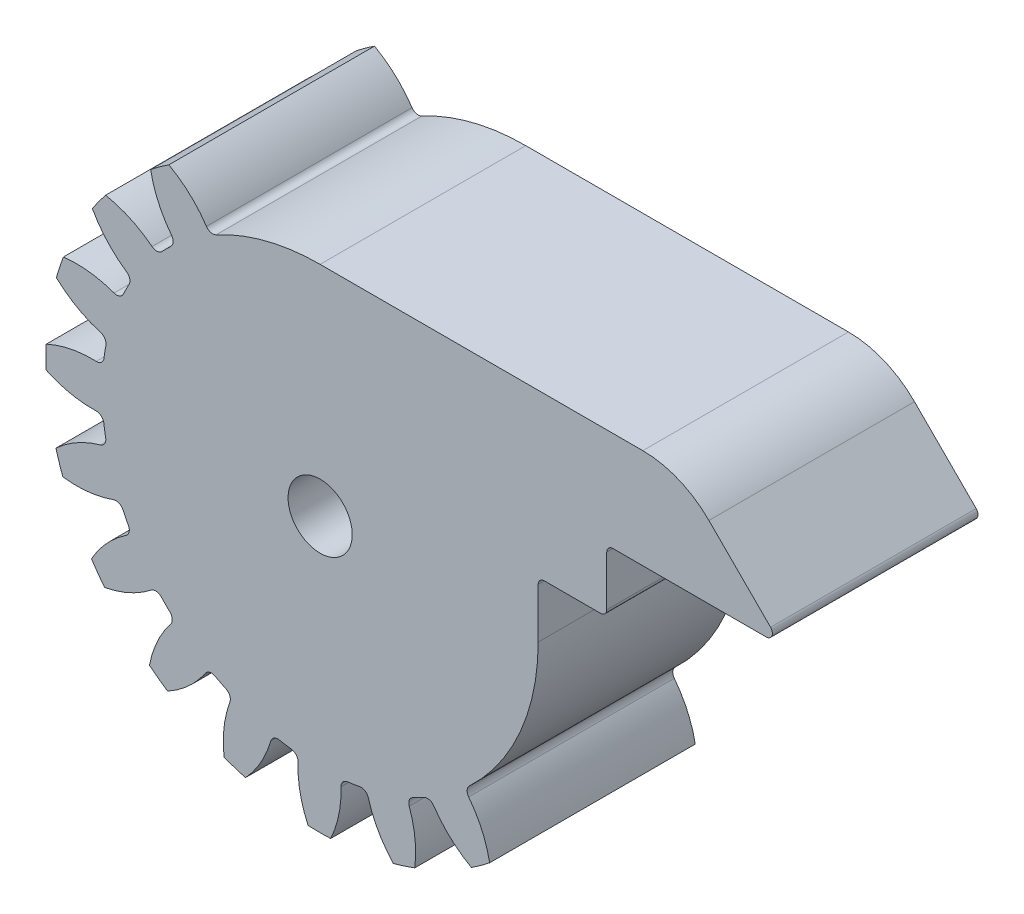
SolidWorks part; units mm, degrees
material "1023 Carbon Steel Sheet (SS)"
ref_plane "Front Plane" through (0, 0, 0) normal (0, 0, 1) x (1, 0, 0)
ref_plane "Top Plane" through (0, 0, 0) normal (0, 1, 0) x (1, 0, 0)
ref_plane "Right Plane" through (0, 0, 0) normal (1, 0, 0) x (0, 0, -1)
sketch "skBase" plane through (0, 0, 0) normal (0, 0, 1) x (1, 0, 0)
  circle A0 centre (0, 0) radius 20
  circle A1 centre (0, 0) radius 22
  circle A2 centre (0, 0) radius 17.5
  dimension "D1" = 40
  dimension "D3" = 4.5
extrude "Base" add sketch "skBase" along normal mid plane 16.5 contours A1
sketch "skToothProfile" plane through (0, 0, 0) normal (0, 0, 1) x (1, 0, 0)
  line L0 (0, 0) -> (0, 22) construction
  line L1 (-1.5692, 19.9383) -> (1.5692, 19.9383) construction
  line L2 (-1.0563, 17.4681) -> (0, 0) construction
  line L3 (0, 15.6271) -> (-2.6287, 22.8493) construction
  line L4 (0, 0) -> (3.4416, 21.7291) construction
  line L5 (1.5692, 19.9383) -> (4.6689, 19.4474) construction
  circle A0 centre (0, 0) radius 22 construction
  arc A1 (-1.0563, 17.4681) -> (-3.258, 22.7681) centre (-9.8105, 16.9387) ccw
  arc A2 (1.0563, 17.4681) -> (3.258, 22.7681) centre (9.8105, 16.9387) cw
  circle A3 centre (0, 0) radius 17.5 construction
  arc A4 (1.0563, 17.4681) -> (-1.0563, 17.4681) centre (0, 0) ccw
  circle A5 centre (0, 0) radius 20 construction
  circle A6 centre (0, 0) radius 22 construction
  circle A7 centre (0, 0) radius 23
  arc A8 (3.258, 22.7681) -> (-3.258, 22.7681) centre (0, 0) ccw
  dimension "D2" = 20
  dimension "D3" = 9
extrude "ToothProfile" cut sketch "skToothProfile" against normal through all and the other way through all
fillet "FilletToothProfile" radius 0.6 2 edges at (1.0563, 17.4681, 0) (-1.0563, 17.4681, 0)
pattern_circular "CirPatternTeeth" count 20 over 360 about axis through (0, 0, 8.25) along (0, 0, 1) of "ToothProfile", "FilletToothProfile"
sketch "skChaveta" plane through (0, 0, 8.25) normal (0, 0, 1) x (1, 0, 0)
  line L0 (0, 2.575) -> (0, 0) construction
  circle A0 centre (0, 0) radius 2.575
  dimension "D1" = 5.15
extrude "Chaveta" cut sketch "skChaveta" against normal through all contours A0
sketch "skRebaixo" plane through (0, 0, 8.25) normal (0, 0, 1) x (1, 0, 0)
  circle A0 centre (0, 0) radius 21.5
  circle A1 centre (0, 0) radius 7.5
  dimension "D1" = 43
  dimension "D2" = 15
sketch "Sketch4" plane through (0, 0, -8.25) normal (0, 0, -1) x (-1, 0, 0)
  circle A0 centre (0, 0) radius 17.5
  arc A5 (-2.5459, 21.8522) -> (-4.3314, 21.5694) centre (0, 0) ccw
  arc A6 (-2.5459, 21.8522) -> (-4.3314, 21.5694) centre (0, 0) ccw
  arc A7 (-18.0189, -1.107) -> (-21.8522, -2.5459) centre (-16.9387, -9.8105) ccw
  arc A8 (-18.0189, -1.107) -> (-21.8522, -2.5459) centre (-16.9387, -9.8105) ccw
  arc A9 (-21.5694, -4.3314) -> (-17.4791, -4.5153) centre (-19.1413, 4.096) ccw
  arc A10 (-21.5694, -4.3314) -> (-17.4791, -4.5153) centre (-19.1413, 4.096) ccw
  arc A127 (-19.996, -9.174) -> (-19.1752, -10.7848) centre (0, 0) ccw
  arc A128 (-19.996, -9.174) -> (-19.1752, -10.7848) centre (0, 0) ccw
  arc A129 (-16.1824, -14.904) -> (-14.904, -16.1824) centre (0, 0) ccw
  arc A130 (-16.1824, -14.904) -> (-14.904, -16.1824) centre (0, 0) ccw
  arc A131 (-10.7848, -19.1752) -> (-9.174, -19.996) centre (0, 0) ccw
  arc A132 (-10.7848, -19.1752) -> (-9.174, -19.996) centre (0, 0) ccw
  arc A133 (-4.3314, -21.5694) -> (-2.5459, -21.8522) centre (0, 0) ccw
  arc A134 (-4.3314, -21.5694) -> (-2.5459, -21.8522) centre (0, 0) ccw
  arc A135 (2.5459, -21.8522) -> (4.3314, -21.5694) centre (0, 0) ccw
  arc A136 (2.5459, -21.8522) -> (4.3314, -21.5694) centre (0, 0) ccw
  arc A137 (9.174, -19.996) -> (10.7848, -19.1752) centre (0, 0) ccw
  arc A138 (9.174, -19.996) -> (10.7848, -19.1752) centre (0, 0) ccw
  arc A139 (14.904, -16.1824) -> (16.1824, -14.904) centre (0, 0) ccw
  arc A140 (14.904, -16.1824) -> (16.1824, -14.904) centre (0, 0) ccw
  arc A141 (19.1752, -10.7848) -> (19.996, -9.174) centre (0, 0) ccw
  arc A142 (19.1752, -10.7848) -> (19.996, -9.174) centre (0, 0) ccw
  arc A143 (21.5694, -4.3314) -> (21.8522, -2.5459) centre (0, 0) ccw
  arc A144 (21.5694, -4.3314) -> (21.8522, -2.5459) centre (0, 0) ccw
  arc A145 (21.8522, 2.5459) -> (21.5694, 4.3314) centre (0, 0) ccw
  arc A146 (21.8522, 2.5459) -> (21.5694, 4.3314) centre (0, 0) ccw
  arc A147 (19.996, 9.174) -> (19.1752, 10.7848) centre (0, 0) ccw
  arc A148 (19.996, 9.174) -> (19.1752, 10.7848) centre (0, 0) ccw
  arc A149 (16.1824, 14.904) -> (14.904, 16.1824) centre (0, 0) ccw
  arc A150 (16.1824, 14.904) -> (14.904, 16.1824) centre (0, 0) ccw
  arc A151 (10.7848, 19.1752) -> (9.174, 19.996) centre (0, 0) ccw
  arc A152 (10.7848, 19.1752) -> (9.174, 19.996) centre (0, 0) ccw
  arc A153 (4.3314, 21.5694) -> (2.5459, 21.8522) centre (0, 0) ccw
  arc A154 (4.3314, 21.5694) -> (2.5459, 21.8522) centre (0, 0) ccw
  arc A155 (-9.174, 19.996) -> (-10.7848, 19.1752) centre (0, 0) ccw
  arc A156 (-9.174, 19.996) -> (-10.7848, 19.1752) centre (0, 0) ccw
  arc A157 (-14.904, 16.1824) -> (-16.1824, 14.904) centre (0, 0) ccw
  arc A158 (-14.904, 16.1824) -> (-16.1824, 14.904) centre (0, 0) ccw
  arc A159 (-19.1752, 10.7848) -> (-19.996, 9.174) centre (0, 0) ccw
  arc A160 (-19.1752, 10.7848) -> (-19.996, 9.174) centre (0, 0) ccw
  arc A161 (-21.5694, 4.3314) -> (-21.8522, 2.5459) centre (0, 0) ccw
  arc A162 (-21.5694, 4.3314) -> (-21.8522, 2.5459) centre (0, 0) ccw
  arc A163 (-4.3314, 21.5694) -> (-4.5153, 17.4791) centre (4.096, 19.1413) ccw
  arc A164 (-4.3314, 21.5694) -> (-4.5153, 17.4791) centre (4.096, 19.1413) ccw
  arc A165 (-4.9352, 16.7897) -> (-4.5153, 17.4791) centre (-5.1044, 17.3653) ccw
  arc A166 (-4.9352, 16.7897) -> (-4.5153, 17.4791) centre (-5.1044, 17.3653) ccw
  arc A167 (-4.9352, 16.7897) -> (-5.8761, 16.484) centre (0, 0) ccw
  arc A168 (-4.9352, 16.7897) -> (-5.8761, 16.484) centre (0, 0) ccw
  arc A169 (-6.621, 16.7949) -> (-5.8761, 16.484) centre (-6.0775, 17.0492) ccw
  arc A170 (-6.621, 16.7949) -> (-5.8761, 16.484) centre (-6.0775, 17.0492) ccw
  arc A171 (-6.621, 16.7949) -> (-9.174, 19.996) centre (-14.5647, 13.0781) ccw
  arc A172 (-6.621, 16.7949) -> (-9.174, 19.996) centre (-14.5647, 13.0781) ccw
  arc A173 (-10.7848, 19.1752) -> (-9.6956, 15.2283) centre (-2.0195, 19.4702) ccw
  arc A174 (-10.7848, 19.1752) -> (-9.6956, 15.2283) centre (-2.0195, 19.4702) ccw
  arc A175 (-9.882, 14.4429) -> (-9.6956, 15.2283) centre (-10.2208, 14.9381) ccw
  arc A176 (-9.882, 14.4429) -> (-9.6956, 15.2283) centre (-10.2208, 14.9381) ccw
  arc A177 (-9.882, 14.4429) -> (-10.6823, 13.8614) centre (0, 0) ccw
  arc A178 (-9.882, 14.4429) -> (-10.6823, 13.8614) centre (0, 0) ccw
  arc A179 (-11.4868, 13.9269) -> (-10.6823, 13.8614) centre (-11.0486, 14.3366) ccw
  arc A180 (-11.4868, 13.9269) -> (-10.6823, 13.8614) centre (-11.0486, 14.3366) ccw
  arc A181 (-11.4868, 13.9269) -> (-14.904, 16.1824) centre (-17.8932, 7.9372) ccw
  arc A182 (-11.4868, 13.9269) -> (-14.904, 16.1824) centre (-17.8932, 7.9372) ccw
  arc A183 (-16.1824, 14.904) -> (-13.9269, 11.4868) centre (-7.9372, 17.8932) ccw
  arc A184 (-16.1824, 14.904) -> (-13.9269, 11.4868) centre (-7.9372, 17.8932) ccw
  arc A185 (-13.8614, 10.6823) -> (-13.9269, 11.4868) centre (-14.3366, 11.0486) ccw
  arc A186 (-13.8614, 10.6823) -> (-13.9269, 11.4868) centre (-14.3366, 11.0486) ccw
  arc A187 (-13.8614, 10.6823) -> (-14.4429, 9.882) centre (0, 0) ccw
  arc A188 (-13.8614, 10.6823) -> (-14.4429, 9.882) centre (0, 0) ccw
  arc A189 (-15.2283, 9.6956) -> (-14.4429, 9.882) centre (-14.9381, 10.2208) ccw
  arc A190 (-15.2283, 9.6956) -> (-14.4429, 9.882) centre (-14.9381, 10.2208) ccw
  arc A191 (-15.2283, 9.6956) -> (-19.1752, 10.7848) centre (-19.4702, 2.0195) ccw
  arc A192 (-15.2283, 9.6956) -> (-19.1752, 10.7848) centre (-19.4702, 2.0195) ccw
  arc A193 (-19.996, 9.174) -> (-16.7949, 6.621) centre (-13.0781, 14.5647) ccw
  arc A194 (-19.996, 9.174) -> (-16.7949, 6.621) centre (-13.0781, 14.5647) ccw
  arc A195 (-16.484, 5.8761) -> (-16.7949, 6.621) centre (-17.0492, 6.0775) ccw
  arc A196 (-16.484, 5.8761) -> (-16.7949, 6.621) centre (-17.0492, 6.0775) ccw
  arc A197 (-16.484, 5.8761) -> (-16.7897, 4.9352) centre (0, 0) ccw
  arc A198 (-16.484, 5.8761) -> (-16.7897, 4.9352) centre (0, 0) ccw
  arc A199 (-17.4791, 4.5153) -> (-16.7897, 4.9352) centre (-17.3653, 5.1044) ccw
  arc A200 (-17.4791, 4.5153) -> (-16.7897, 4.9352) centre (-17.3653, 5.1044) ccw
  arc A201 (-17.4791, 4.5153) -> (-21.5694, 4.3314) centre (-19.1413, -4.096) ccw
  arc A202 (-17.4791, 4.5153) -> (-21.5694, 4.3314) centre (-19.1413, -4.096) ccw
  arc A203 (-21.8522, 2.5459) -> (-18.0189, 1.107) centre (-16.9387, 9.8105) ccw
  arc A204 (-21.8522, 2.5459) -> (-18.0189, 1.107) centre (-16.9387, 9.8105) ccw
  arc A205 (-17.493, 0.4946) -> (-18.0189, 1.107) centre (-18.0928, 0.5116) ccw
  arc A206 (-17.493, 0.4946) -> (-18.0189, 1.107) centre (-18.0928, 0.5116) ccw
  arc A207 (-17.493, 0.4946) -> (-17.493, -0.4946) centre (0, 0) ccw
  arc A208 (-17.493, 0.4946) -> (-17.493, -0.4946) centre (0, 0) ccw
  arc A209 (-18.0189, -1.107) -> (-17.493, -0.4946) centre (-18.0928, -0.5116) ccw
  arc A210 (-18.0189, -1.107) -> (-17.493, -0.4946) centre (-18.0928, -0.5116) ccw
  arc A211 (-16.7897, -4.9352) -> (-17.4791, -4.5153) centre (-17.3653, -5.1044) ccw
  arc A212 (-16.7897, -4.9352) -> (-17.4791, -4.5153) centre (-17.3653, -5.1044) ccw
  arc A213 (-16.7897, -4.9352) -> (-16.484, -5.8761) centre (0, 0) ccw
  arc A214 (-16.7897, -4.9352) -> (-16.484, -5.8761) centre (0, 0) ccw
  arc A215 (-16.7949, -6.621) -> (-16.484, -5.8761) centre (-17.0492, -6.0775) ccw
  arc A216 (-16.7949, -6.621) -> (-16.484, -5.8761) centre (-17.0492, -6.0775) ccw
  arc A217 (-16.7949, -6.621) -> (-19.996, -9.174) centre (-13.0781, -14.5647) ccw
  arc A218 (-16.7949, -6.621) -> (-19.996, -9.174) centre (-13.0781, -14.5647) ccw
  arc A219 (-19.1752, -10.7848) -> (-15.2283, -9.6956) centre (-19.4702, -2.0195) ccw
  arc A220 (-19.1752, -10.7848) -> (-15.2283, -9.6956) centre (-19.4702, -2.0195) ccw
  arc A221 (-14.4429, -9.882) -> (-15.2283, -9.6956) centre (-14.9381, -10.2208) ccw
  arc A222 (-14.4429, -9.882) -> (-15.2283, -9.6956) centre (-14.9381, -10.2208) ccw
  arc A223 (-14.4429, -9.882) -> (-13.8614, -10.6823) centre (0, 0) ccw
  arc A224 (-14.4429, -9.882) -> (-13.8614, -10.6823) centre (0, 0) ccw
  arc A225 (-13.9269, -11.4868) -> (-13.8614, -10.6823) centre (-14.3366, -11.0486) ccw
  arc A226 (-13.9269, -11.4868) -> (-13.8614, -10.6823) centre (-14.3366, -11.0486) ccw
  arc A227 (-13.9269, -11.4868) -> (-16.1824, -14.904) centre (-7.9372, -17.8932) ccw
  arc A228 (-13.9269, -11.4868) -> (-16.1824, -14.904) centre (-7.9372, -17.8932) ccw
  arc A229 (-14.904, -16.1824) -> (-11.4868, -13.9269) centre (-17.8932, -7.9372) ccw
  arc A230 (-14.904, -16.1824) -> (-11.4868, -13.9269) centre (-17.8932, -7.9372) ccw
  arc A231 (-10.6823, -13.8614) -> (-11.4868, -13.9269) centre (-11.0486, -14.3366) ccw
  arc A232 (-10.6823, -13.8614) -> (-11.4868, -13.9269) centre (-11.0486, -14.3366) ccw
  arc A233 (-10.6823, -13.8614) -> (-9.882, -14.4429) centre (0, 0) ccw
  arc A234 (-10.6823, -13.8614) -> (-9.882, -14.4429) centre (0, 0) ccw
  arc A235 (-9.6956, -15.2283) -> (-9.882, -14.4429) centre (-10.2208, -14.9381) ccw
  arc A236 (-9.6956, -15.2283) -> (-9.882, -14.4429) centre (-10.2208, -14.9381) ccw
  arc A237 (-9.6956, -15.2283) -> (-10.7848, -19.1752) centre (-2.0195, -19.4702) ccw
  arc A238 (-9.6956, -15.2283) -> (-10.7848, -19.1752) centre (-2.0195, -19.4702) ccw
  arc A239 (-9.174, -19.996) -> (-6.621, -16.7949) centre (-14.5647, -13.0781) ccw
  arc A240 (-9.174, -19.996) -> (-6.621, -16.7949) centre (-14.5647, -13.0781) ccw
  arc A241 (-5.8761, -16.484) -> (-6.621, -16.7949) centre (-6.0775, -17.0492) ccw
  arc A242 (-5.8761, -16.484) -> (-6.621, -16.7949) centre (-6.0775, -17.0492) ccw
  arc A243 (-5.8761, -16.484) -> (-4.9352, -16.7897) centre (0, 0) ccw
  arc A244 (-5.8761, -16.484) -> (-4.9352, -16.7897) centre (0, 0) ccw
  arc A245 (-4.5153, -17.4791) -> (-4.9352, -16.7897) centre (-5.1044, -17.3653) ccw
  arc A246 (-4.5153, -17.4791) -> (-4.9352, -16.7897) centre (-5.1044, -17.3653) ccw
  arc A247 (-4.5153, -17.4791) -> (-4.3314, -21.5694) centre (4.096, -19.1413) ccw
  arc A248 (-4.5153, -17.4791) -> (-4.3314, -21.5694) centre (4.096, -19.1413) ccw
  arc A249 (-2.5459, -21.8522) -> (-1.107, -18.0189) centre (-9.8105, -16.9387) ccw
  arc A250 (-2.5459, -21.8522) -> (-1.107, -18.0189) centre (-9.8105, -16.9387) ccw
  arc A251 (-0.4946, -17.493) -> (-1.107, -18.0189) centre (-0.5116, -18.0928) ccw
  arc A252 (-0.4946, -17.493) -> (-1.107, -18.0189) centre (-0.5116, -18.0928) ccw
  arc A253 (-0.4946, -17.493) -> (0.4946, -17.493) centre (0, 0) ccw
  arc A254 (-0.4946, -17.493) -> (0.4946, -17.493) centre (0, 0) ccw
  arc A255 (1.107, -18.0189) -> (0.4946, -17.493) centre (0.5116, -18.0928) ccw
  arc A256 (1.107, -18.0189) -> (0.4946, -17.493) centre (0.5116, -18.0928) ccw
  arc A257 (1.107, -18.0189) -> (2.5459, -21.8522) centre (9.8105, -16.9387) ccw
  arc A258 (1.107, -18.0189) -> (2.5459, -21.8522) centre (9.8105, -16.9387) ccw
  arc A259 (4.3314, -21.5694) -> (4.5153, -17.4791) centre (-4.096, -19.1413) ccw
  arc A260 (4.3314, -21.5694) -> (4.5153, -17.4791) centre (-4.096, -19.1413) ccw
  arc A261 (4.9352, -16.7897) -> (4.5153, -17.4791) centre (5.1044, -17.3653) ccw
  arc A262 (4.9352, -16.7897) -> (4.5153, -17.4791) centre (5.1044, -17.3653) ccw
  arc A263 (4.9352, -16.7897) -> (5.8761, -16.484) centre (0, 0) ccw
  arc A264 (4.9352, -16.7897) -> (5.8761, -16.484) centre (0, 0) ccw
  arc A265 (6.621, -16.7949) -> (5.8761, -16.484) centre (6.0775, -17.0492) ccw
  arc A266 (6.621, -16.7949) -> (5.8761, -16.484) centre (6.0775, -17.0492) ccw
  arc A267 (6.621, -16.7949) -> (9.174, -19.996) centre (14.5647, -13.0781) ccw
  arc A268 (6.621, -16.7949) -> (9.174, -19.996) centre (14.5647, -13.0781) ccw
  arc A269 (10.7848, -19.1752) -> (9.6956, -15.2283) centre (2.0195, -19.4702) ccw
  arc A270 (10.7848, -19.1752) -> (9.6956, -15.2283) centre (2.0195, -19.4702) ccw
  arc A271 (9.882, -14.4429) -> (9.6956, -15.2283) centre (10.2208, -14.9381) ccw
  arc A272 (9.882, -14.4429) -> (9.6956, -15.2283) centre (10.2208, -14.9381) ccw
  arc A273 (9.882, -14.4429) -> (10.6823, -13.8614) centre (0, 0) ccw
  arc A274 (9.882, -14.4429) -> (10.6823, -13.8614) centre (0, 0) ccw
  arc A275 (11.4868, -13.9269) -> (10.6823, -13.8614) centre (11.0486, -14.3366) ccw
  arc A276 (11.4868, -13.9269) -> (10.6823, -13.8614) centre (11.0486, -14.3366) ccw
  arc A277 (11.4868, -13.9269) -> (14.904, -16.1824) centre (17.8932, -7.9372) ccw
  arc A278 (11.4868, -13.9269) -> (14.904, -16.1824) centre (17.8932, -7.9372) ccw
  arc A279 (16.1824, -14.904) -> (13.9269, -11.4868) centre (7.9372, -17.8932) ccw
  arc A280 (16.1824, -14.904) -> (13.9269, -11.4868) centre (7.9372, -17.8932) ccw
  arc A281 (13.8614, -10.6823) -> (13.9269, -11.4868) centre (14.3366, -11.0486) ccw
  arc A282 (13.8614, -10.6823) -> (13.9269, -11.4868) centre (14.3366, -11.0486) ccw
  arc A283 (13.8614, -10.6823) -> (14.4429, -9.882) centre (0, 0) ccw
  arc A284 (13.8614, -10.6823) -> (14.4429, -9.882) centre (0, 0) ccw
  arc A285 (15.2283, -9.6956) -> (14.4429, -9.882) centre (14.9381, -10.2208) ccw
  arc A286 (15.2283, -9.6956) -> (14.4429, -9.882) centre (14.9381, -10.2208) ccw
  arc A287 (15.2283, -9.6956) -> (19.1752, -10.7848) centre (19.4702, -2.0195) ccw
  arc A288 (15.2283, -9.6956) -> (19.1752, -10.7848) centre (19.4702, -2.0195) ccw
  arc A289 (19.996, -9.174) -> (16.7949, -6.621) centre (13.0781, -14.5647) ccw
  arc A290 (19.996, -9.174) -> (16.7949, -6.621) centre (13.0781, -14.5647) ccw
  arc A291 (16.484, -5.8761) -> (16.7949, -6.621) centre (17.0492, -6.0775) ccw
  arc A292 (16.484, -5.8761) -> (16.7949, -6.621) centre (17.0492, -6.0775) ccw
  arc A293 (16.484, -5.8761) -> (16.7897, -4.9352) centre (0, 0) ccw
  arc A294 (16.484, -5.8761) -> (16.7897, -4.9352) centre (0, 0) ccw
  arc A295 (17.4791, -4.5153) -> (16.7897, -4.9352) centre (17.3653, -5.1044) ccw
  arc A296 (17.4791, -4.5153) -> (16.7897, -4.9352) centre (17.3653, -5.1044) ccw
  arc A297 (17.4791, -4.5153) -> (21.5694, -4.3314) centre (19.1413, 4.096) ccw
  arc A298 (17.4791, -4.5153) -> (21.5694, -4.3314) centre (19.1413, 4.096) ccw
  arc A299 (21.8522, -2.5459) -> (18.0189, -1.107) centre (16.9387, -9.8105) ccw
  arc A300 (21.8522, -2.5459) -> (18.0189, -1.107) centre (16.9387, -9.8105) ccw
  arc A301 (17.493, -0.4946) -> (18.0189, -1.107) centre (18.0928, -0.5116) ccw
  arc A302 (17.493, -0.4946) -> (18.0189, -1.107) centre (18.0928, -0.5116) ccw
  arc A303 (17.493, -0.4946) -> (17.493, 0.4946) centre (0, 0) ccw
  arc A304 (17.493, -0.4946) -> (17.493, 0.4946) centre (0, 0) ccw
  arc A305 (18.0189, 1.107) -> (17.493, 0.4946) centre (18.0928, 0.5116) ccw
  arc A306 (18.0189, 1.107) -> (17.493, 0.4946) centre (18.0928, 0.5116) ccw
  arc A307 (18.0189, 1.107) -> (21.8522, 2.5459) centre (16.9387, 9.8105) ccw
  arc A308 (18.0189, 1.107) -> (21.8522, 2.5459) centre (16.9387, 9.8105) ccw
  arc A309 (21.5694, 4.3314) -> (17.4791, 4.5153) centre (19.1413, -4.096) ccw
  arc A310 (21.5694, 4.3314) -> (17.4791, 4.5153) centre (19.1413, -4.096) ccw
  arc A311 (-21.8522, -2.5459) -> (-21.5694, -4.3314) centre (0, 0) ccw
  arc A312 (-21.8522, -2.5459) -> (-21.5694, -4.3314) centre (0, 0) ccw
  arc A313 (16.7897, 4.9352) -> (17.4791, 4.5153) centre (17.3653, 5.1044) ccw
  arc A314 (16.7897, 4.9352) -> (17.4791, 4.5153) centre (17.3653, 5.1044) ccw
  arc A315 (16.7897, 4.9352) -> (16.484, 5.8761) centre (0, 0) ccw
  arc A316 (16.7897, 4.9352) -> (16.484, 5.8761) centre (0, 0) ccw
  arc A317 (16.7949, 6.621) -> (16.484, 5.8761) centre (17.0492, 6.0775) ccw
  arc A318 (16.7949, 6.621) -> (16.484, 5.8761) centre (17.0492, 6.0775) ccw
  arc A319 (16.7949, 6.621) -> (19.996, 9.174) centre (13.0781, 14.5647) ccw
  arc A320 (16.7949, 6.621) -> (19.996, 9.174) centre (13.0781, 14.5647) ccw
  arc A321 (19.1752, 10.7848) -> (15.2283, 9.6956) centre (19.4702, 2.0195) ccw
  arc A322 (19.1752, 10.7848) -> (15.2283, 9.6956) centre (19.4702, 2.0195) ccw
  arc A323 (14.4429, 9.882) -> (15.2283, 9.6956) centre (14.9381, 10.2208) ccw
  arc A324 (14.4429, 9.882) -> (15.2283, 9.6956) centre (14.9381, 10.2208) ccw
  arc A325 (14.4429, 9.882) -> (13.8614, 10.6823) centre (0, 0) ccw
  arc A326 (14.4429, 9.882) -> (13.8614, 10.6823) centre (0, 0) ccw
  arc A327 (13.9269, 11.4868) -> (13.8614, 10.6823) centre (14.3366, 11.0486) ccw
  arc A328 (13.9269, 11.4868) -> (13.8614, 10.6823) centre (14.3366, 11.0486) ccw
  arc A329 (13.9269, 11.4868) -> (16.1824, 14.904) centre (7.9372, 17.8932) ccw
  arc A330 (13.9269, 11.4868) -> (16.1824, 14.904) centre (7.9372, 17.8932) ccw
  arc A331 (14.904, 16.1824) -> (11.4868, 13.9269) centre (17.8932, 7.9372) ccw
  arc A332 (14.904, 16.1824) -> (11.4868, 13.9269) centre (17.8932, 7.9372) ccw
  arc A333 (10.6823, 13.8614) -> (11.4868, 13.9269) centre (11.0486, 14.3366) ccw
  arc A334 (10.6823, 13.8614) -> (11.4868, 13.9269) centre (11.0486, 14.3366) ccw
  arc A335 (10.6823, 13.8614) -> (9.882, 14.4429) centre (0, 0) ccw
  arc A336 (10.6823, 13.8614) -> (9.882, 14.4429) centre (0, 0) ccw
  arc A337 (9.6956, 15.2283) -> (9.882, 14.4429) centre (10.2208, 14.9381) ccw
  arc A338 (9.6956, 15.2283) -> (9.882, 14.4429) centre (10.2208, 14.9381) ccw
  arc A339 (9.6956, 15.2283) -> (10.7848, 19.1752) centre (2.0195, 19.4702) ccw
  arc A340 (9.6956, 15.2283) -> (10.7848, 19.1752) centre (2.0195, 19.4702) ccw
  arc A341 (9.174, 19.996) -> (6.621, 16.7949) centre (14.5647, 13.0781) ccw
  arc A342 (9.174, 19.996) -> (6.621, 16.7949) centre (14.5647, 13.0781) ccw
  arc A343 (5.8761, 16.484) -> (6.621, 16.7949) centre (6.0775, 17.0492) ccw
  arc A344 (5.8761, 16.484) -> (6.621, 16.7949) centre (6.0775, 17.0492) ccw
  arc A345 (5.8761, 16.484) -> (4.9352, 16.7897) centre (0, 0) ccw
  arc A346 (5.8761, 16.484) -> (4.9352, 16.7897) centre (0, 0) ccw
  arc A347 (4.5153, 17.4791) -> (4.9352, 16.7897) centre (5.1044, 17.3653) ccw
  arc A348 (4.5153, 17.4791) -> (4.9352, 16.7897) centre (5.1044, 17.3653) ccw
  arc A349 (4.5153, 17.4791) -> (4.3314, 21.5694) centre (-4.096, 19.1413) ccw
  arc A350 (4.5153, 17.4791) -> (4.3314, 21.5694) centre (-4.096, 19.1413) ccw
  arc A351 (2.5459, 21.8522) -> (1.107, 18.0189) centre (9.8105, 16.9387) ccw
  arc A352 (2.5459, 21.8522) -> (1.107, 18.0189) centre (9.8105, 16.9387) ccw
  arc A353 (0.4946, 17.493) -> (1.107, 18.0189) centre (0.5116, 18.0928) ccw
  arc A354 (0.4946, 17.493) -> (1.107, 18.0189) centre (0.5116, 18.0928) ccw
  arc A355 (0.4946, 17.493) -> (-0.4946, 17.493) centre (0, 0) ccw
  arc A356 (0.4946, 17.493) -> (-0.4946, 17.493) centre (0, 0) ccw
  arc A357 (-1.107, 18.0189) -> (-0.4946, 17.493) centre (-0.5116, 18.0928) ccw
  arc A358 (-1.107, 18.0189) -> (-0.4946, 17.493) centre (-0.5116, 18.0928) ccw
  arc A359 (-1.107, 18.0189) -> (-2.5459, 21.8522) centre (-9.8105, 16.9387) ccw
  arc A360 (-1.107, 18.0189) -> (-2.5459, 21.8522) centre (-9.8105, 16.9387) ccw
  dimension "D1" = 0
sketch "Sketch6" plane through (0, 0, -8.25) normal (0, 0, -1) x (-1, 0, 0)
  circle A0 centre (0, 0) radius 20 construction
  dimension "D1" = 40
move or copy body "Body-Move/Copy1" bodies to move or copy 104 copy no rotation origin (0, 0, 0) rotation axis (0, 0, 1) rotation angle 8.84
sketch "Sketch7" plane through (0, 0, -8.25) normal (0, 0, -1) x (-1, 0, 0)
  circle A0 centre (0, 0) radius 17.5
  arc A120 (0.8425, 21.9839) -> (-0.9653, 21.9788) centre (0, 0) ccw
  arc A121 (-0.9653, 21.9788) -> (-1.7755, 17.9653) centre (6.9889, 18.2845) ccw
  arc A122 (-2.2964, 17.3487) -> (-1.7755, 17.9653) centre (-2.3751, 17.9435) ccw
  arc A123 (-2.2964, 17.3487) -> (-3.2731, 17.1912) centre (0, 0) ccw
  arc A124 (-3.9614, 17.6129) -> (-3.2731, 17.1912) centre (-3.3853, 17.7806) ccw
  arc A125 (-3.9614, 17.6129) -> (-5.9921, 21.1683) centre (-12.3819, 15.161) ccw
  arc A126 (-5.9921, 21.1683) -> (-7.7099, 20.6048) centre (0, 0) ccw
  arc A127 (-7.7099, 20.6048) -> (-7.2402, 16.5374) centre (0.9966, 19.5493) ccw
  arc A128 (-7.545, 15.7899) -> (-7.2402, 16.5374) centre (-7.8037, 16.3313) ccw
  arc A129 (-7.545, 15.7899) -> (-8.4253, 15.3384) centre (0, 0) ccw
  arc A130 (-9.2102, 15.5267) -> (-8.4253, 15.3384) centre (-8.7141, 15.8642) ccw
  arc A131 (-9.2102, 15.5267) -> (-12.2402, 18.2805) centre (-16.4609, 10.5927) ccw
  arc A132 (-12.2402, 18.2805) -> (-13.6998, 17.2138) centre (0, 0) ccw
  arc A133 (-13.6998, 17.2138) -> (-11.9962, 13.4906) centre (-5.0932, 18.9004) ccw
  arc A134 (-12.0551, 12.6856) -> (-11.9962, 13.4906) centre (-12.4684, 13.1205) ccw
  arc A135 (-12.0551, 12.6856) -> (-12.7527, 11.9841) centre (0, 0) ccw
  arc A136 (-13.5574, 11.9207) -> (-12.7527, 11.9841) centre (-13.1899, 12.395) ccw
  arc A137 (-13.5574, 11.9207) -> (-17.2901, 13.6034) centre (-18.9286, 4.9876) ccw
  arc A138 (-17.2901, 13.6034) -> (-18.3486, 12.1379) centre (0, 0) ccw
  arc A139 (-18.3486, 12.1379) -> (-15.5779, 9.1233) centre (-10.6845, 16.4015) ccw
  arc A140 (-15.3852, 8.3395) -> (-15.5779, 9.1233) centre (-15.9127, 8.6254) ccw
  arc A141 (-15.3852, 8.3395) -> (-15.8318, 7.4567) centre (0, 0) ccw
  arc A142 (-16.5775, 7.1478) -> (-15.8318, 7.4567) centre (-16.3746, 7.7124) ccw
  arc A143 (-16.5775, 7.1478) -> (-20.6475, 7.5947) centre (-19.5434, -1.1058) ccw
  arc A144 (-20.6475, 7.5947) -> (-21.2014, 5.8738) centre (0, 0) ccw
  arc A145 (-21.2014, 5.8738) -> (-17.6347, 3.863) centre (-15.2299, 12.2971) ccw
  arc A146 (-17.2092, 3.177) -> (-17.6347, 3.863) centre (-17.7992, 3.2859) ccw
  arc A147 (-17.2092, 3.177) -> (-17.3612, 2.1995) centre (0, 0) ccw
  arc A148 (-17.975, 1.6752) -> (-17.3612, 2.1995) centre (-17.9565, 2.2749) ccw
  arc A149 (-17.975, 1.6752) -> (-21.9839, 0.8425) centre (-18.2452, -7.0909) ccw
  arc A150 (-21.9839, 0.8425) -> (-21.9788, -0.9653) centre (0, 0) ccw
  arc A151 (-21.9788, -0.9653) -> (-17.9653, -1.7755) centre (-18.2845, 6.9889) ccw
  arc A152 (-17.3487, -2.2964) -> (-17.9653, -1.7755) centre (-17.9435, -2.3751) ccw
  arc A153 (-17.3487, -2.2964) -> (-17.1912, -3.2731) centre (0, 0) ccw
  arc A154 (-17.6129, -3.9614) -> (-17.1912, -3.2731) centre (-17.7806, -3.3853) ccw
  arc A155 (-17.6129, -3.9614) -> (-21.1683, -5.9921) centre (-15.161, -12.3819) ccw
  arc A156 (-21.1683, -5.9921) -> (-20.6048, -7.7099) centre (0, 0) ccw
  arc A157 (-20.6048, -7.7099) -> (-16.5374, -7.2402) centre (-19.5493, 0.9966) ccw
  arc A158 (-15.7899, -7.545) -> (-16.5374, -7.2402) centre (-16.3313, -7.8037) ccw
  arc A159 (-15.7899, -7.545) -> (-15.3384, -8.4253) centre (0, 0) ccw
  arc A160 (-15.5267, -9.2102) -> (-15.3384, -8.4253) centre (-15.8642, -8.7141) ccw
  arc A161 (-15.5267, -9.2102) -> (-18.2805, -12.2402) centre (-10.5927, -16.4609) ccw
  arc A162 (-18.2805, -12.2402) -> (-17.2138, -13.6998) centre (0, 0) ccw
  arc A163 (-17.2138, -13.6998) -> (-13.4906, -11.9962) centre (-18.9004, -5.0932) ccw
  arc A164 (-12.6856, -12.0551) -> (-13.4906, -11.9962) centre (-13.1205, -12.4684) ccw
  arc A165 (-12.6856, -12.0551) -> (-11.9841, -12.7527) centre (0, 0) ccw
  arc A166 (-11.9207, -13.5574) -> (-11.9841, -12.7527) centre (-12.395, -13.1899) ccw
  arc A167 (-11.9207, -13.5574) -> (-13.6034, -17.2901) centre (-4.9876, -18.9286) ccw
  arc A168 (-13.6034, -17.2901) -> (-12.1379, -18.3486) centre (0, 0) ccw
  arc A169 (-12.1379, -18.3486) -> (-9.1233, -15.5779) centre (-16.4015, -10.6845) ccw
  arc A170 (-8.3395, -15.3852) -> (-9.1233, -15.5779) centre (-8.6254, -15.9127) ccw
  arc A171 (-8.3395, -15.3852) -> (-7.4567, -15.8318) centre (0, 0) ccw
  arc A172 (-7.1478, -16.5775) -> (-7.4567, -15.8318) centre (-7.7124, -16.3746) ccw
  arc A173 (-7.1478, -16.5775) -> (-7.5947, -20.6475) centre (1.1058, -19.5434) ccw
  arc A174 (-7.5947, -20.6475) -> (-5.8738, -21.2014) centre (0, 0) ccw
  arc A175 (-5.8738, -21.2014) -> (-3.863, -17.6347) centre (-12.2971, -15.2299) ccw
  arc A176 (-3.177, -17.2092) -> (-3.863, -17.6347) centre (-3.2859, -17.7992) ccw
  arc A177 (-3.177, -17.2092) -> (-2.1995, -17.3612) centre (0, 0) ccw
  arc A178 (-1.6752, -17.975) -> (-2.1995, -17.3612) centre (-2.2749, -17.9565) ccw
  arc A179 (-1.6752, -17.975) -> (-0.8425, -21.9839) centre (7.0909, -18.2452) ccw
  arc A180 (-0.8425, -21.9839) -> (0.9653, -21.9788) centre (0, 0) ccw
  arc A181 (0.9653, -21.9788) -> (1.7755, -17.9653) centre (-6.9889, -18.2845) ccw
  arc A182 (2.2964, -17.3487) -> (1.7755, -17.9653) centre (2.3751, -17.9435) ccw
  arc A183 (2.2964, -17.3487) -> (3.2731, -17.1912) centre (0, 0) ccw
  arc A184 (3.9614, -17.6129) -> (3.2731, -17.1912) centre (3.3853, -17.7806) ccw
  arc A185 (3.9614, -17.6129) -> (5.9921, -21.1683) centre (12.3819, -15.161) ccw
  arc A186 (5.9921, -21.1683) -> (7.7099, -20.6048) centre (0, 0) ccw
  arc A187 (7.7099, -20.6048) -> (7.2402, -16.5374) centre (-0.9966, -19.5493) ccw
  arc A188 (7.545, -15.7899) -> (7.2402, -16.5374) centre (7.8037, -16.3313) ccw
  arc A189 (7.545, -15.7899) -> (8.4253, -15.3384) centre (0, 0) ccw
  arc A190 (9.2102, -15.5267) -> (8.4253, -15.3384) centre (8.7141, -15.8642) ccw
  arc A191 (9.2102, -15.5267) -> (12.2402, -18.2805) centre (16.4609, -10.5927) ccw
  arc A192 (12.2402, -18.2805) -> (13.6998, -17.2138) centre (0, 0) ccw
  arc A193 (13.6998, -17.2138) -> (11.9962, -13.4906) centre (5.0932, -18.9004) ccw
  arc A194 (12.0551, -12.6856) -> (11.9962, -13.4906) centre (12.4684, -13.1205) ccw
  arc A195 (12.0551, -12.6856) -> (12.7527, -11.9841) centre (0, 0) ccw
  arc A196 (13.5574, -11.9207) -> (12.7527, -11.9841) centre (13.1899, -12.395) ccw
  arc A197 (13.5574, -11.9207) -> (17.2901, -13.6034) centre (18.9286, -4.9876) ccw
  arc A198 (17.2901, -13.6034) -> (18.3486, -12.1379) centre (0, 0) ccw
  arc A199 (18.3486, -12.1379) -> (15.5779, -9.1233) centre (10.6845, -16.4015) ccw
  arc A200 (15.3852, -8.3395) -> (15.5779, -9.1233) centre (15.9127, -8.6254) ccw
  arc A201 (15.3852, -8.3395) -> (15.8318, -7.4567) centre (0, 0) ccw
  arc A202 (16.5775, -7.1478) -> (15.8318, -7.4567) centre (16.3746, -7.7124) ccw
  arc A203 (16.5775, -7.1478) -> (20.6475, -7.5947) centre (19.5434, 1.1058) ccw
  arc A204 (20.6475, -7.5947) -> (21.2014, -5.8738) centre (0, 0) ccw
  arc A205 (21.2014, -5.8738) -> (17.6347, -3.863) centre (15.2299, -12.2971) ccw
  arc A206 (17.2092, -3.177) -> (17.6347, -3.863) centre (17.7992, -3.2859) ccw
  arc A207 (17.2092, -3.177) -> (17.3612, -2.1995) centre (0, 0) ccw
  arc A208 (17.975, -1.6752) -> (17.3612, -2.1995) centre (17.9565, -2.2749) ccw
  arc A209 (17.975, -1.6752) -> (21.9839, -0.8425) centre (18.2452, 7.0909) ccw
  arc A210 (21.9839, -0.8425) -> (21.9788, 0.9653) centre (0, 0) ccw
  arc A211 (21.9788, 0.9653) -> (17.9653, 1.7755) centre (18.2845, -6.9889) ccw
  arc A212 (17.3487, 2.2964) -> (17.9653, 1.7755) centre (17.9435, 2.3751) ccw
  arc A213 (17.3487, 2.2964) -> (17.1912, 3.2731) centre (0, 0) ccw
  arc A214 (17.6129, 3.9614) -> (17.1912, 3.2731) centre (17.7806, 3.3853) ccw
  arc A215 (17.6129, 3.9614) -> (21.1683, 5.9921) centre (15.161, 12.3819) ccw
  arc A216 (21.1683, 5.9921) -> (20.6048, 7.7099) centre (0, 0) ccw
  arc A217 (20.6048, 7.7099) -> (16.5374, 7.2402) centre (19.5493, -0.9966) ccw
  arc A218 (15.7899, 7.545) -> (16.5374, 7.2402) centre (16.3313, 7.8037) ccw
  arc A219 (15.7899, 7.545) -> (15.3384, 8.4253) centre (0, 0) ccw
  arc A220 (15.5267, 9.2102) -> (15.3384, 8.4253) centre (15.8642, 8.7141) ccw
  arc A221 (15.5267, 9.2102) -> (18.2805, 12.2402) centre (10.5927, 16.4609) ccw
  arc A222 (18.2805, 12.2402) -> (17.2138, 13.6998) centre (0, 0) ccw
  arc A223 (17.2138, 13.6998) -> (13.4906, 11.9962) centre (18.9004, 5.0932) ccw
  arc A224 (12.6856, 12.0551) -> (13.4906, 11.9962) centre (13.1205, 12.4684) ccw
  arc A225 (12.6856, 12.0551) -> (11.9841, 12.7527) centre (0, 0) ccw
  arc A226 (11.9207, 13.5574) -> (11.9841, 12.7527) centre (12.395, 13.1899) ccw
  arc A227 (11.9207, 13.5574) -> (13.6034, 17.2901) centre (4.9876, 18.9286) ccw
  arc A228 (13.6034, 17.2901) -> (12.1379, 18.3486) centre (0, 0) ccw
  arc A229 (12.1379, 18.3486) -> (9.1233, 15.5779) centre (16.4015, 10.6845) ccw
  arc A230 (8.3395, 15.3852) -> (9.1233, 15.5779) centre (8.6254, 15.9127) ccw
  arc A231 (8.3395, 15.3852) -> (7.4567, 15.8318) centre (0, 0) ccw
  arc A232 (7.1478, 16.5775) -> (7.4567, 15.8318) centre (7.7124, 16.3746) ccw
  arc A233 (7.1478, 16.5775) -> (7.5947, 20.6475) centre (-1.1058, 19.5434) ccw
  arc A234 (7.5947, 20.6475) -> (5.8738, 21.2014) centre (0, 0) ccw
  arc A235 (5.8738, 21.2014) -> (3.863, 17.6347) centre (12.2971, 15.2299) ccw
  arc A236 (3.177, 17.2092) -> (3.863, 17.6347) centre (3.2859, 17.7992) ccw
  arc A237 (3.177, 17.2092) -> (2.1995, 17.3612) centre (0, 0) ccw
  arc A238 (1.6752, 17.975) -> (2.1995, 17.3612) centre (2.2749, 17.9565) ccw
  arc A239 (1.6752, 17.975) -> (0.8425, 21.9839) centre (-7.0909, 18.2452) ccw
  arc A240 (0.8425, 21.9839) -> (-0.9653, 21.9788) centre (0, 0) ccw
  arc A241 (-0.9653, 21.9788) -> (-1.7755, 17.9653) centre (6.9889, 18.2845) ccw
  arc A242 (-2.2964, 17.3487) -> (-1.7755, 17.9653) centre (-2.3751, 17.9435) ccw
  arc A243 (-2.2964, 17.3487) -> (-3.2731, 17.1912) centre (0, 0) ccw
  arc A244 (-3.9614, 17.6129) -> (-3.2731, 17.1912) centre (-3.3853, 17.7806) ccw
  arc A245 (-3.9614, 17.6129) -> (-5.9921, 21.1683) centre (-12.3819, 15.161) ccw
  arc A246 (-5.9921, 21.1683) -> (-7.7099, 20.6048) centre (0, 0) ccw
  arc A247 (-7.7099, 20.6048) -> (-7.2402, 16.5374) centre (0.9966, 19.5493) ccw
  arc A248 (-7.545, 15.7899) -> (-7.2402, 16.5374) centre (-7.8037, 16.3313) ccw
  arc A249 (-7.545, 15.7899) -> (-8.4253, 15.3384) centre (0, 0) ccw
  arc A250 (-9.2102, 15.5267) -> (-8.4253, 15.3384) centre (-8.7141, 15.8642) ccw
  arc A251 (-9.2102, 15.5267) -> (-12.2402, 18.2805) centre (-16.4609, 10.5927) ccw
  arc A252 (-12.2402, 18.2805) -> (-13.6998, 17.2138) centre (0, 0) ccw
  arc A253 (-13.6998, 17.2138) -> (-11.9962, 13.4906) centre (-5.0932, 18.9004) ccw
  arc A254 (-12.0551, 12.6856) -> (-11.9962, 13.4906) centre (-12.4684, 13.1205) ccw
  arc A255 (-12.0551, 12.6856) -> (-12.7527, 11.9841) centre (0, 0) ccw
  arc A256 (-13.5574, 11.9207) -> (-12.7527, 11.9841) centre (-13.1899, 12.395) ccw
  arc A257 (-13.5574, 11.9207) -> (-17.2901, 13.6034) centre (-18.9286, 4.9876) ccw
  arc A258 (-17.2901, 13.6034) -> (-18.3486, 12.1379) centre (0, 0) ccw
  arc A259 (-18.3486, 12.1379) -> (-15.5779, 9.1233) centre (-10.6845, 16.4015) ccw
  arc A260 (-15.3852, 8.3395) -> (-15.5779, 9.1233) centre (-15.9127, 8.6254) ccw
  arc A261 (-15.3852, 8.3395) -> (-15.8318, 7.4567) centre (0, 0) ccw
  arc A262 (-16.5775, 7.1478) -> (-15.8318, 7.4567) centre (-16.3746, 7.7124) ccw
  arc A263 (-16.5775, 7.1478) -> (-20.6475, 7.5947) centre (-19.5434, -1.1058) ccw
  arc A264 (-20.6475, 7.5947) -> (-21.2014, 5.8738) centre (0, 0) ccw
  arc A265 (-21.2014, 5.8738) -> (-17.6347, 3.863) centre (-15.2299, 12.2971) ccw
  arc A266 (-17.2092, 3.177) -> (-17.6347, 3.863) centre (-17.7992, 3.2859) ccw
  arc A267 (-17.2092, 3.177) -> (-17.3612, 2.1995) centre (0, 0) ccw
  arc A268 (-17.975, 1.6752) -> (-17.3612, 2.1995) centre (-17.9565, 2.2749) ccw
  arc A269 (-17.975, 1.6752) -> (-21.9839, 0.8425) centre (-18.2452, -7.0909) ccw
  arc A270 (-21.9839, 0.8425) -> (-21.9788, -0.9653) centre (0, 0) ccw
  arc A271 (-21.9788, -0.9653) -> (-17.9653, -1.7755) centre (-18.2845, 6.9889) ccw
  arc A272 (-17.3487, -2.2964) -> (-17.9653, -1.7755) centre (-17.9435, -2.3751) ccw
  arc A273 (-17.3487, -2.2964) -> (-17.1912, -3.2731) centre (0, 0) ccw
  arc A274 (-17.6129, -3.9614) -> (-17.1912, -3.2731) centre (-17.7806, -3.3853) ccw
  arc A275 (-17.6129, -3.9614) -> (-21.1683, -5.9921) centre (-15.161, -12.3819) ccw
  arc A276 (-21.1683, -5.9921) -> (-20.6048, -7.7099) centre (0, 0) ccw
  arc A277 (-20.6048, -7.7099) -> (-16.5374, -7.2402) centre (-19.5493, 0.9966) ccw
  arc A278 (-15.7899, -7.545) -> (-16.5374, -7.2402) centre (-16.3313, -7.8037) ccw
  arc A279 (-15.7899, -7.545) -> (-15.3384, -8.4253) centre (0, 0) ccw
  arc A280 (-15.5267, -9.2102) -> (-15.3384, -8.4253) centre (-15.8642, -8.7141) ccw
  arc A281 (-15.5267, -9.2102) -> (-18.2805, -12.2402) centre (-10.5927, -16.4609) ccw
  arc A282 (-18.2805, -12.2402) -> (-17.2138, -13.6998) centre (0, 0) ccw
  arc A283 (-17.2138, -13.6998) -> (-13.4906, -11.9962) centre (-18.9004, -5.0932) ccw
  arc A284 (-12.6856, -12.0551) -> (-13.4906, -11.9962) centre (-13.1205, -12.4684) ccw
  arc A285 (-12.6856, -12.0551) -> (-11.9841, -12.7527) centre (0, 0) ccw
  arc A286 (-11.9207, -13.5574) -> (-11.9841, -12.7527) centre (-12.395, -13.1899) ccw
  arc A287 (-11.9207, -13.5574) -> (-13.6034, -17.2901) centre (-4.9876, -18.9286) ccw
  arc A288 (-13.6034, -17.2901) -> (-12.1379, -18.3486) centre (0, 0) ccw
  arc A289 (-12.1379, -18.3486) -> (-9.1233, -15.5779) centre (-16.4015, -10.6845) ccw
  arc A290 (-8.3395, -15.3852) -> (-9.1233, -15.5779) centre (-8.6254, -15.9127) ccw
  arc A291 (-8.3395, -15.3852) -> (-7.4567, -15.8318) centre (0, 0) ccw
  arc A292 (-7.1478, -16.5775) -> (-7.4567, -15.8318) centre (-7.7124, -16.3746) ccw
  arc A293 (-7.1478, -16.5775) -> (-7.5947, -20.6475) centre (1.1058, -19.5434) ccw
  arc A294 (-7.5947, -20.6475) -> (-5.8738, -21.2014) centre (0, 0) ccw
  arc A295 (-5.8738, -21.2014) -> (-3.863, -17.6347) centre (-12.2971, -15.2299) ccw
  arc A296 (-3.177, -17.2092) -> (-3.863, -17.6347) centre (-3.2859, -17.7992) ccw
  arc A297 (-3.177, -17.2092) -> (-2.1995, -17.3612) centre (0, 0) ccw
  arc A298 (-1.6752, -17.975) -> (-2.1995, -17.3612) centre (-2.2749, -17.9565) ccw
  arc A299 (-1.6752, -17.975) -> (-0.8425, -21.9839) centre (7.0909, -18.2452) ccw
  arc A300 (-0.8425, -21.9839) -> (0.9653, -21.9788) centre (0, 0) ccw
  arc A301 (0.9653, -21.9788) -> (1.7755, -17.9653) centre (-6.9889, -18.2845) ccw
  arc A302 (2.2964, -17.3487) -> (1.7755, -17.9653) centre (2.3751, -17.9435) ccw
  arc A303 (2.2964, -17.3487) -> (3.2731, -17.1912) centre (0, 0) ccw
  arc A304 (3.9614, -17.6129) -> (3.2731, -17.1912) centre (3.3853, -17.7806) ccw
  arc A305 (3.9614, -17.6129) -> (5.9921, -21.1683) centre (12.3819, -15.161) ccw
  arc A306 (5.9921, -21.1683) -> (7.7099, -20.6048) centre (0, 0) ccw
  arc A307 (7.7099, -20.6048) -> (7.2402, -16.5374) centre (-0.9966, -19.5493) ccw
  arc A308 (7.545, -15.7899) -> (7.2402, -16.5374) centre (7.8037, -16.3313) ccw
  arc A309 (7.545, -15.7899) -> (8.4253, -15.3384) centre (0, 0) ccw
  arc A310 (9.2102, -15.5267) -> (8.4253, -15.3384) centre (8.7141, -15.8642) ccw
  arc A311 (9.2102, -15.5267) -> (12.2402, -18.2805) centre (16.4609, -10.5927) ccw
  arc A312 (12.2402, -18.2805) -> (13.6998, -17.2138) centre (0, 0) ccw
  arc A313 (13.6998, -17.2138) -> (11.9962, -13.4906) centre (5.0932, -18.9004) ccw
  arc A314 (12.0551, -12.6856) -> (11.9962, -13.4906) centre (12.4684, -13.1205) ccw
  arc A315 (12.0551, -12.6856) -> (12.7527, -11.9841) centre (0, 0) ccw
  arc A316 (13.5574, -11.9207) -> (12.7527, -11.9841) centre (13.1899, -12.395) ccw
  arc A317 (13.5574, -11.9207) -> (17.2901, -13.6034) centre (18.9286, -4.9876) ccw
  arc A318 (17.2901, -13.6034) -> (18.3486, -12.1379) centre (0, 0) ccw
  arc A319 (18.3486, -12.1379) -> (15.5779, -9.1233) centre (10.6845, -16.4015) ccw
  arc A320 (15.3852, -8.3395) -> (15.5779, -9.1233) centre (15.9127, -8.6254) ccw
  arc A321 (15.3852, -8.3395) -> (15.8318, -7.4567) centre (0, 0) ccw
  arc A322 (16.5775, -7.1478) -> (15.8318, -7.4567) centre (16.3746, -7.7124) ccw
  arc A323 (16.5775, -7.1478) -> (20.6475, -7.5947) centre (19.5434, 1.1058) ccw
  arc A324 (20.6475, -7.5947) -> (21.2014, -5.8738) centre (0, 0) ccw
  arc A325 (21.2014, -5.8738) -> (17.6347, -3.863) centre (15.2299, -12.2971) ccw
  arc A326 (17.2092, -3.177) -> (17.6347, -3.863) centre (17.7992, -3.2859) ccw
  arc A327 (17.2092, -3.177) -> (17.3612, -2.1995) centre (0, 0) ccw
  arc A328 (17.975, -1.6752) -> (17.3612, -2.1995) centre (17.9565, -2.2749) ccw
  arc A329 (17.975, -1.6752) -> (21.9839, -0.8425) centre (18.2452, 7.0909) ccw
  arc A330 (21.9839, -0.8425) -> (21.9788, 0.9653) centre (0, 0) ccw
  arc A331 (21.9788, 0.9653) -> (17.9653, 1.7755) centre (18.2845, -6.9889) ccw
  arc A332 (17.3487, 2.2964) -> (17.9653, 1.7755) centre (17.9435, 2.3751) ccw
  arc A333 (17.3487, 2.2964) -> (17.1912, 3.2731) centre (0, 0) ccw
  arc A334 (17.6129, 3.9614) -> (17.1912, 3.2731) centre (17.7806, 3.3853) ccw
  arc A335 (17.6129, 3.9614) -> (21.1683, 5.9921) centre (15.161, 12.3819) ccw
  arc A336 (21.1683, 5.9921) -> (20.6048, 7.7099) centre (0, 0) ccw
  arc A337 (20.6048, 7.7099) -> (16.5374, 7.2402) centre (19.5493, -0.9966) ccw
  arc A338 (15.7899, 7.545) -> (16.5374, 7.2402) centre (16.3313, 7.8037) ccw
  arc A339 (15.7899, 7.545) -> (15.3384, 8.4253) centre (0, 0) ccw
  arc A340 (15.5267, 9.2102) -> (15.3384, 8.4253) centre (15.8642, 8.7141) ccw
  arc A341 (15.5267, 9.2102) -> (18.2805, 12.2402) centre (10.5927, 16.4609) ccw
  arc A342 (18.2805, 12.2402) -> (17.2138, 13.6998) centre (0, 0) ccw
  arc A343 (17.2138, 13.6998) -> (13.4906, 11.9962) centre (18.9004, 5.0932) ccw
  arc A344 (12.6856, 12.0551) -> (13.4906, 11.9962) centre (13.1205, 12.4684) ccw
  arc A345 (12.6856, 12.0551) -> (11.9841, 12.7527) centre (0, 0) ccw
  arc A346 (11.9207, 13.5574) -> (11.9841, 12.7527) centre (12.395, 13.1899) ccw
  arc A347 (11.9207, 13.5574) -> (13.6034, 17.2901) centre (4.9876, 18.9286) ccw
  arc A348 (13.6034, 17.2901) -> (12.1379, 18.3486) centre (0, 0) ccw
  arc A349 (12.1379, 18.3486) -> (9.1233, 15.5779) centre (16.4015, 10.6845) ccw
  arc A350 (8.3395, 15.3852) -> (9.1233, 15.5779) centre (8.6254, 15.9127) ccw
  arc A351 (8.3395, 15.3852) -> (7.4567, 15.8318) centre (0, 0) ccw
  arc A352 (7.1478, 16.5775) -> (7.4567, 15.8318) centre (7.7124, 16.3746) ccw
  arc A353 (7.1478, 16.5775) -> (7.5947, 20.6475) centre (-1.1058, 19.5434) ccw
  arc A354 (7.5947, 20.6475) -> (5.8738, 21.2014) centre (0, 0) ccw
  arc A355 (5.8738, 21.2014) -> (3.863, 17.6347) centre (12.2971, 15.2299) ccw
  arc A356 (3.177, 17.2092) -> (3.863, 17.6347) centre (3.2859, 17.7992) ccw
  arc A357 (3.177, 17.2092) -> (2.1995, 17.3612) centre (0, 0) ccw
  arc A358 (1.6752, 17.975) -> (2.1995, 17.3612) centre (2.2749, 17.9565) ccw
  arc A359 (1.6752, 17.975) -> (0.8425, 21.9839) centre (-7.0909, 18.2452) ccw
  dimension "D1" = 0
extrude "Cut-Extrude1" cut sketch "Sketch7" against normal blind 16.5 contours A266 A0 A262 A263 A264 A265 | A272 A0 A268 A269 A270 A271 | A278 A0 A274 A275 A276 A277 | A260 A0 A256 A257 A258 A259 | A284 A0 A280 A281 A282 A283 | A254 A0 A250 A251 A252 A253 | A248 A0 A244 A245 A246 A247 | A358 A359 A240 A241 A242 A0 | A356 A0 A352 A353 A354 A355 region at (-5.9793, 18.5787, -8.25) region at (0.0545, 19.5171, -8.25) region at (6.083, 18.545, -8.25) region at (11.516, 15.7577, -8.25) region at (15.8217, 11.4278, -8.25) region at (15.7577, -11.516, -8.25) region at (18.5787, 5.9793, -8.25) region at (18.545, -6.083, -8.25) region at (19.5171, -0.0545, -8.25)
sketch "Sketch8" plane through (0, 0, -8.25) normal (0, 0, -1) x (-1, 0, 0)
  line L1 (-17.5, 7.125) -> (-2.575, 7.125)
  line L2 (-17.5, 7.125) -> (-17.5, -7.125)
  line L3 (-17.5, -7.125) -> (-2.575, -7.125)
  line L4 (-2.575, 7.125) -> (-2.575, -7.125)
  circle A0 centre (0, 0) radius 2.575 construction
  arc A1 (8.3395, 15.3852) -> (-11.9841, -12.7527) centre (0, 0) ccw construction
  point P6 (-2.575, 0)
  dimension "D1" = 14.25
sketch "Sketch9" plane through (0, 0, -8.25) normal (0, 0, -1) x (-1, 0, 0)
  line L0 (-17.5, 0) -> (-17.5, 4.5)
  line L1 (-17.5, 4.5) -> (-23, 4.5)
  line L2 (-23, 4.5) -> (-23, 9.5)
  line L3 (-23, 9.5) -> (-37, 9.5)
  line L4 (-37, 9.5) -> (-29, 17.5)
  line L5 (-29, 17.5) -> (0, 17.5)
  arc A0 (8.3395, 15.3852) -> (-11.9841, -12.7527) centre (0, 0) ccw construction
  arc A4 (0, 17.5) -> (-17.5, 0) centre (0, 0) ccw
  point P5 (-30, 9.5)
  dimension "D1" = 14
  dimension "D3" = 45
  dimension "D4" = 9.5
  dimension "D5" = 30
  dimension "D6" = 5
extrude "Boss-Extrude1" add sketch "Sketch9" against normal blind 16.5
sketch "Sketch10" plane through (0, 0, -8.25) normal (0, 0, -1) x (-1, 0, 0)
  circle A0 centre (0, 0) radius 2.575 construction
  circle A1 centre (0, 0) radius 2.575
  circle A2 centre (0, 0) radius 5
  dimension "D1" = 10
extrude "Boss-Extrude2" add sketch "Sketch10" along normal blind 1.65
fillet "Fillet1" radius 0.5 4 edges at (17.5, 4.5, 0) (23, 4.5, 0) (23, 9.5, 0) (37, 9.5, 0)
fillet "Fillet2" radius 7.5 1 edges at (29, 17.5, 0)
equation "\"Module\"= 2mm"
equation "\"Number_Of_Teeth\"= 20"
equation "\"D1@skBase\"=\"Module\" * \"Number_Of_Teeth\""
equation "\"D2@skBase\"=\"Module\""
equation "\"D3@skBase\"=\"Module\" * if( \"Module\" >=1.25, 2.25, 2.4)"
equation "\"Pressure_Angle\"= 20deg"
equation "\"D2@skToothProfile\"=\"Pressure_Angle\""
equation "\"D3@skToothProfile\"=180 / \"Number_Of_Teeth\""
equation "\"D1@FilletToothProfile\"= 0.3 * \"Module\""
equation "\"D1@CirPatternTeeth\"=\"Number_Of_Teeth\""
equation "\"Width\"= 16.5mm"
equation "\"D1@Base\"=\"Width\""
equation "\"D1@Cut-Extrude1\"=\"Width\""
equation "\"D1@Boss-Extrude1\"=\"Width\""
